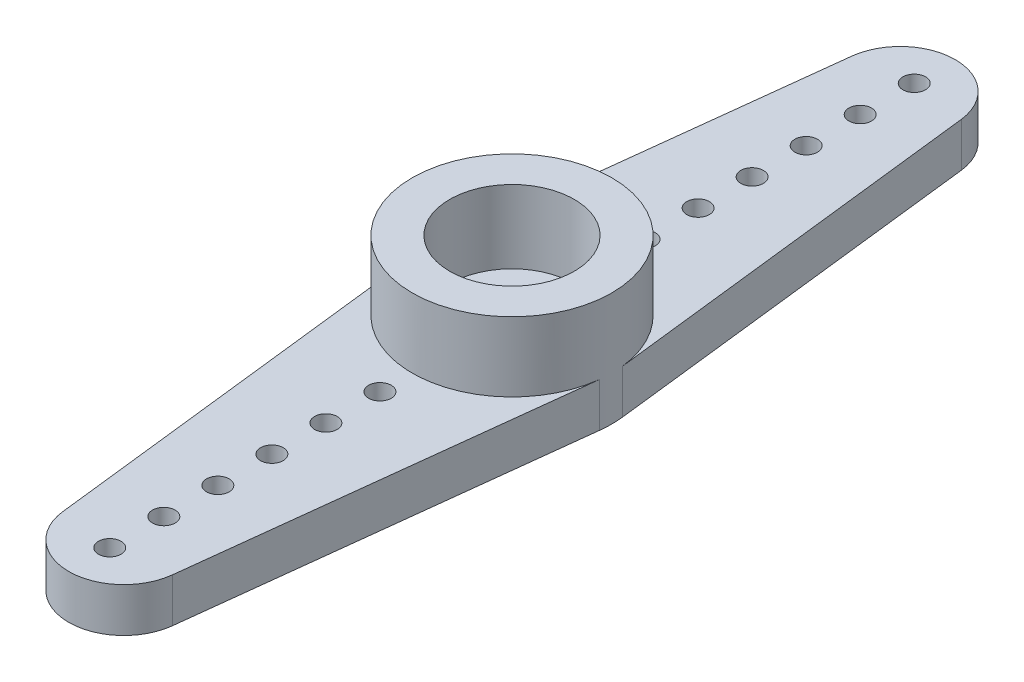
SolidWorks part; units mm, degrees
ref_plane "Front Plane" through (0, 0, 0) normal (0, 0, 1) x (1, 0, 0)
ref_plane "Top Plane" through (0, 0, 0) normal (0, 1, 0) x (1, 0, 0)
ref_plane "Right Plane" through (0, 0, 0) normal (1, 0, 0) x (0, 0, -1)
sketch "Sketch1" plane through (0, 0, 0) normal (0, 1, 0) x (1, 0, 0)
  line L0 (-3.596, 0.4165) -> (-1.9867, 14.3101)
  line L3 (1.9867, 14.3101) -> (3.596, 0.4165)
  line L4 (0, 0) -> (0, 14.08) construction
  line L5 (0, 16.08) -> (0, 14.08) construction
  line L6 (0, 0) -> (0, -3.62) construction
  arc A2 (-3.596, 0.4165) -> (3.596, 0.4165) centre (0, 0) ccw
  arc A3 (1.9867, 14.3101) -> (-1.9867, 14.3101) centre (0, 14.08) ccw
  dimension "D2" = 3.62
  dimension "D3" = 2
  dimension "D1" = 19.7
extrude "Boss-Extrude1" add sketch "Sketch1" along normal blind 1.6
sketch "Sketch2" plane through (0, 1.6, 0) normal (0, 1, 0) x (1, 0, 0)
  circle A0 centre (0, 0) radius 3.62
  arc A1 (-3.596, 0.4165) -> (3.596, 0.4165) centre (0, 0) ccw construction
extrude "Boss-Extrude2" add sketch "Sketch2" along normal offset from surface (2.52 mm away) 4.12 up to face at (0, 0, -6.7967)
sketch "Sketch3" plane through (0, 4.12, 0) normal (0, 1, 0) x (1, 0, 0)
  circle A0 centre (0, 0) radius 2.26
  circle A1 centre (0, 0) radius 3.62 construction
  dimension "D1" = 1.36
sketch "Sketch4" plane through (0, 0, 0) normal (0, -1, 0) x (1, 0, 0)
  circle A1 centre (0, 0) radius 2.26
  circle A2 centre (0, 0) radius 2.26
  dimension "D1" = 0
sketch "Sketch5" plane through (0, 0, 0) normal (0, 1, 0) x (1, 0, 0)
  circle A0 centre (0, 0) radius 1.16
  dimension "D1" = 2.32
sketch "Sketch6" plane through (0, 1.6, 0) normal (0, 1, 0) x (1, 0, 0)
  line L0 (0, 16.08) -> (0, 3.62) construction
  line L1 (0, 3.62) -> (0, -3.62) construction
  arc A0 (1.9867, 14.3101) -> (-1.9867, 14.3101) centre (0, 14.08) ccw construction
  arc A1 (3.596, 0.4165) -> (-3.596, 0.4165) centre (0, 0) ccw construction
  circle A2 centre (0, 4.79) radius 0.41
  circle A3 centre (0, 6.75) radius 0.41
  circle A4 centre (0, 8.71) radius 0.41
  circle A5 centre (0, 10.67) radius 0.41
  circle A6 centre (0, 12.63) radius 0.41
  circle A7 centre (0, 0) radius 3.62 construction
  circle A8 centre (0, 14.59) radius 0.41
  point P10 (0, 4.38)
  point P29 (0, 15)
  dimension "D4" = 0.82
  dimension "D2" = 8
  dimension "D3" = 1.08
  dimension "D1" = 6
extrude "Cut-Extrude5" cut sketch "Sketch6" against normal through all
mirror "Mirror1" about plane through (0, 0, 0) normal (0, 0, 1) of "Cut-Extrude5", "Boss-Extrude1"
extrude "Cut-Extrude9" cut sketch "Sketch5" along normal through all
extrude "Cut-Extrude10" cut sketch "Sketch4" against normal blind 0.8
extrude "Cut-Extrude11" cut sketch "Sketch3" against normal blind 2.65
